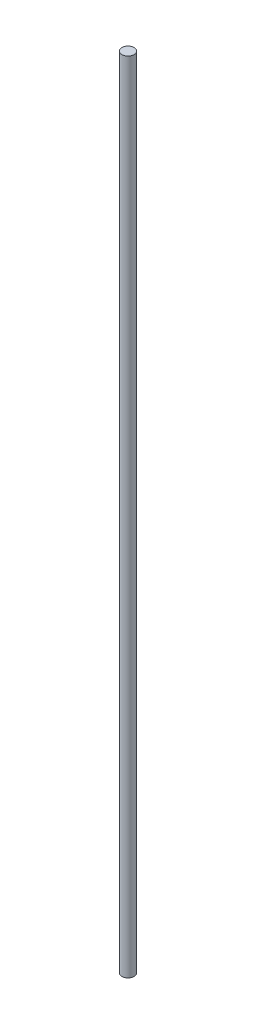
SolidWorks part; units mm, degrees
material "AISI 1020"
ref_plane "Front Plane" through (0, 0, 0) normal (0, 0, 1) x (1, 0, 0)
ref_plane "Top Plane" through (0, 0, 0) normal (0, 1, 0) x (1, 0, 0)
ref_plane "Right Plane" through (0, 0, 0) normal (1, 0, 0) x (0, 0, -1)
sketch "Sketch1" plane through (0, 0, 0) normal (0, 1, 0) x (1, 0, 0)
  circle A0 centre (0, 0) radius 3
  dimension "D1" = 6
extrude "Boss-Extrude1" add sketch "Sketch1" along normal blind 195 and the other way blind 195
cosmetic thread "Cosmetic Thread1" parameters "D2"=5
